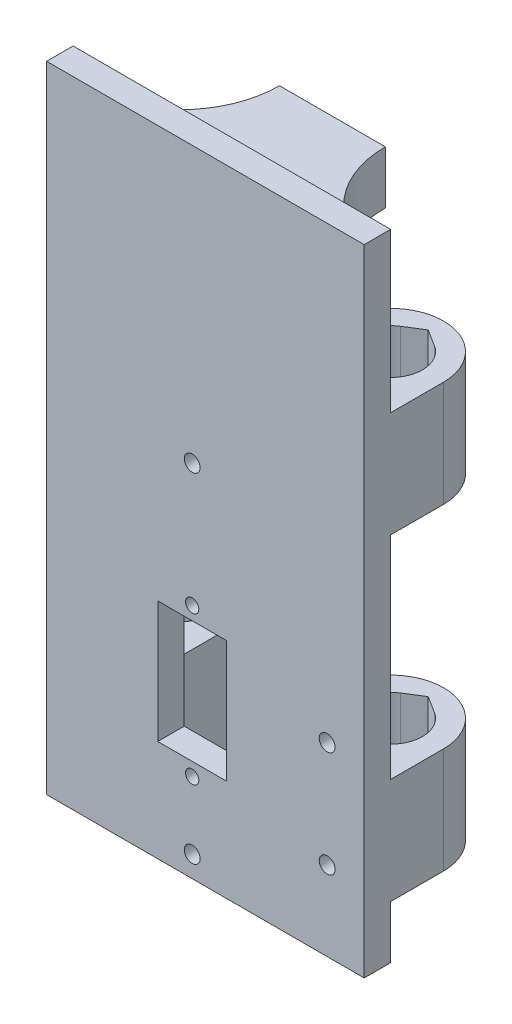
SolidWorks part; units mm, degrees
ref_plane "Спереди" through (0, 0, 0) normal (0, 0, 1) x (1, 0, 0)
ref_plane "Сверху" through (0, 0, 0) normal (0, 1, 0) x (1, 0, 0)
ref_plane "Справа" through (0, 0, 0) normal (1, 0, 0) x (0, 0, -1)
other "Configuration Table"
sketch "Sketch1" plane through (0, 0, 0) normal (0, 0, 1) x (1, 0, 0)
  line L0 (23, -10) -> (23, -60) construction
  line L1 (-30, 60) -> (30, 60)
  line L2 (-30, 60) -> (-30, -60)
  line L3 (-30, -60) -> (30, -60)
  line L4 (30, 60) -> (30, -60)
  line L5 (0, -60) -> (0, 60) construction
  line L6 (-30, 0) -> (30, 0) construction
  line L7 (30, -10) -> (16, -10) construction
  line L8 (30, -10) -> (30, -60) construction
  line L9 (30, -60) -> (16, -60) construction
  line L10 (16, -10) -> (16, -60) construction
  line L11 (22, -60) -> (22, 60) construction
  line L12 (13.5, -60) -> (13.5, 60) construction
  line L13 (-2.5, -60) -> (-2.5, 60) construction
  line L14 (-30, -24) -> (30, -24) construction
  line L16 (-9, -17.8) -> (4, -17.8)
  line L17 (-9, -17.8) -> (-9, -40.8)
  line L18 (-9, -40.8) -> (4, -40.8)
  line L19 (4, -17.8) -> (4, -40.8)
  line L20 (-2.5, -40.8) -> (-2.5, -17.8) construction
  line L21 (-9, -29.3) -> (4, -29.3) construction
  circle A0 centre (23, -25) radius 1.5
  circle A1 centre (23, -45) radius 1.5
  circle A2 centre (-2.5, -56) radius 1.5
  circle A3 centre (-2.5, 8) radius 1.5
  circle A4 centre (-2.5, -15.3) radius 1.25
  circle A5 centre (-2.5, -43.3) radius 1.25
  point P0 (0, 0)
  point P14 (23, -35)
  point P26 (-2.5, -24)
  point P27 (-2.5, -29.3)
  dimension "D5" = 3
  dimension "D8" = 8
  dimension "D11" = 3
  dimension "D18" = 2.5
  dimension "D1" = 60
  dimension "D2" = 120
  dimension "D3" = 14
  dimension "D4" = 50
  dimension "D6" = 20
  dimension "D7" = 10
  dimension "D9" = 8.5
  dimension "D10" = 16
  dimension "D12" = 4
  dimension "D13" = 64
  dimension "D14" = 32
  dimension "D15" = 6.2
  dimension "D16" = 23
  dimension "D17" = 13
  dimension "D19" = 2.5
  dimension "D20" = 2.5
extrude "Boss-Extrude1" add sketch "Sketch1" along normal blind 5
sketch "Sketch2" plane through (0, 0, 0) normal (0, 0, -1) x (-1, 0, 0)
  line L0 (-30, -60) -> (-30, 60) construction
  line L1 (-30, -50) -> (-10, -50)
  line L2 (-30, -50) -> (-30, -30)
  line L3 (-30, -30) -> (-10, -30)
  line L4 (-10, -50) -> (-10, -30)
  line L5 (30, 60) -> (30, -60) construction
  line L6 (30, -50) -> (10, -50)
  line L7 (30, -50) -> (30, -30)
  line L8 (30, -30) -> (10, -30)
  line L9 (10, -50) -> (10, -30)
  line L10 (30, -60) -> (-30, -60) construction
  line L11 (30, 30) -> (10, 30)
  line L12 (30, 30) -> (30, 10)
  line L13 (30, 10) -> (10, 10)
  line L14 (10, 30) -> (10, 10)
  line L15 (-30, 30) -> (-10, 30)
  line L16 (-30, 30) -> (-30, 10)
  line L17 (-30, 10) -> (-10, 10)
  line L18 (-10, 30) -> (-10, 10)
  dimension "D1" = 10
  dimension "D2" = 20
  dimension "D3" = 40
extrude "Boss-Extrude2" add sketch "Sketch2" along normal blind 20
sketch "Sketch3" plane through (0, -50, 0) normal (0, -1, 0) x (1, 0, 0)
  line L0 (-30, 0) -> (-10, -20) construction
  line L1 (30, 0) -> (10, -20) construction
  line L2 (-23.1883, -15.0828) -> (-20, -17.0828)
  line L3 (-20, -17.0828) -> (-16.8117, -15.0828)
  line L4 (0, 0) -> (0, -20) construction
  line L5 (20, -17.0828) -> (16.8117, -15.0828)
  line L6 (23.1883, -15.0828) -> (20, -17.0828)
  circle A0 centre (-20, -10) radius 6 construction
  arc A2 (-23.1883, -15.0828) -> (-16.8117, -15.0828) centre (-20, -10) cw
  circle A3 centre (20, -10) radius 6 construction
  arc A4 (23.1883, -15.0828) -> (16.8117, -15.0828) centre (20, -10) ccw
  dimension "D1" = 12
  dimension "D2" = 2
extrude "Cut-Extrude1" cut sketch "Sketch3" against normal through all
fillet "Fillet1" radius 10 8 edges at (-10, -40, -20) (-30, -40, -20) (-30, 20, -20) (-10, 20, -20) (30, 20, -20) (10, 20, -20) (10, -40, -20) (30, -40, -20)
sketch "Sketch4" plane through (0, 0, 0) normal (0, 0, -1) x (-1, 0, 0)
  line L0 (30, 44) -> (-30, 44) construction
  line L1 (30, 60) -> (30, 30) construction
  line L2 (-30, 30) -> (-30, 60) construction
  line L3 (30, -60) -> (-30, -60) construction
  line L5 (-30, 44) -> (30, 44)
  line L6 (-30, 44) -> (-30, 54)
  line L7 (-30, 54) -> (30, 54)
  line L8 (30, 44) -> (30, 54)
  dimension "D1" = 104
  dimension "D2" = 10
extrude "Boss-Extrude3" add sketch "Sketch4" along normal blind 19
sketch "Sketch5" plane through (0, 54, 0) normal (0, 1, 0) x (1, 0, 0)
  line L0 (-30, 19) -> (0, 0) construction
  line L1 (0, 0) -> (30, 19) construction
  line L2 (-10, 19) -> (-10, 0) construction
  line L3 (-30, 19) -> (30, 19) construction
  line L4 (-30, 0) -> (30, 0) construction
  line L5 (-10, 0) -> (10, 19) construction
  line L6 (10, 19) -> (10, 0) construction
  line L7 (30, 0) -> (-30, 0) construction
  line L8 (-10, 19) -> (-30, 19)
  line L9 (-30, 19) -> (-30, 0)
  line L10 (10, 19) -> (30, 19)
  line L11 (30, 19) -> (30, 0)
  arc A0 (-10, 19) -> (-30, 0) centre (-29.025, 19) cw
  arc A1 (10, 19) -> (30, 0) centre (29.025, 19) ccw
  dimension "D1" = 10
  dimension "D2" = 10
extrude "Cut-Extrude2" cut sketch "Sketch5" against normal blind 10
fillet "Fillet2" radius 3 2 edges at (0, 44, 0) (0, 54, 0)
